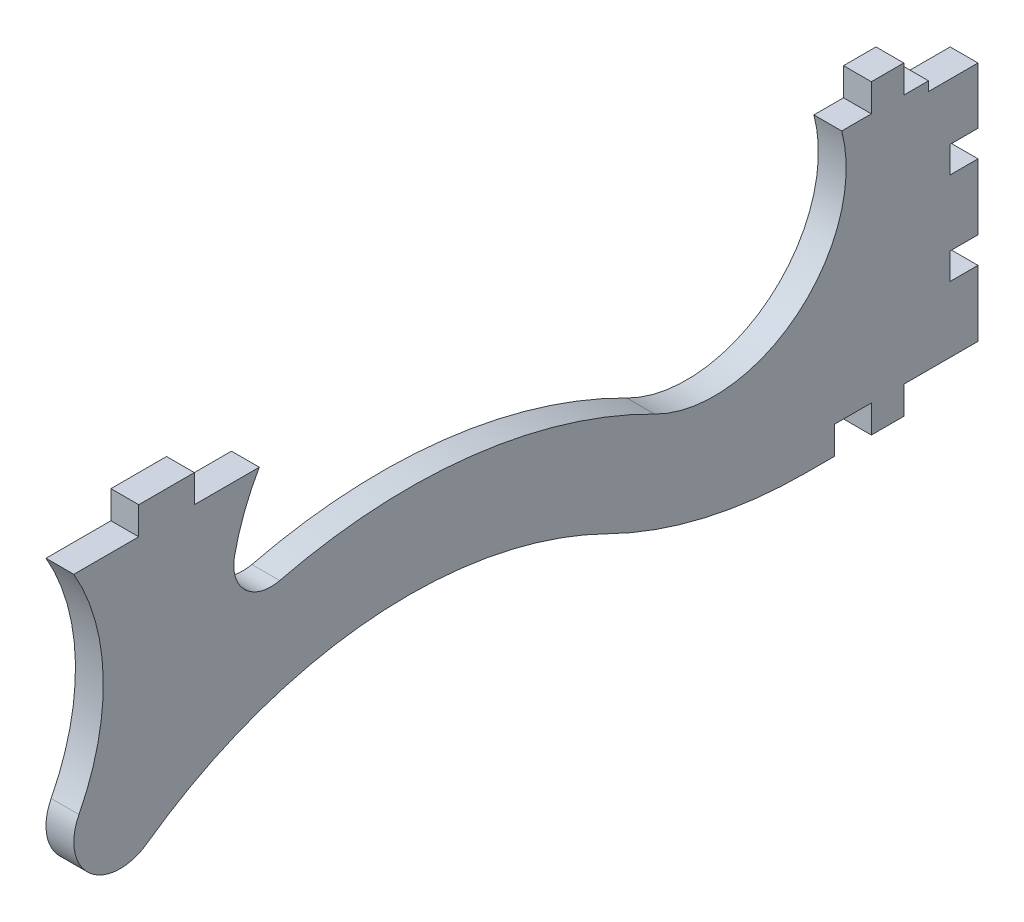
SolidWorks part; units mm, degrees
ref_plane "Front Plane" through (0, 0, 0) normal (0, 0, 1) x (1, 0, 0)
ref_plane "Top Plane" through (0, 0, 0) normal (0, 1, 0) x (1, 0, 0)
ref_plane "Right Plane" through (0, 0, 0) normal (1, 0, 0) x (0, 0, -1)
sketch "Sketch1" plane through (0, 0, 0) normal (1, 0, 0) x (0, 0, -1)
  line L0 (-80, 30) -> (-87, 30)
  line L1 (-87, 30) -> (-87, 33)
  line L2 (-87, 33) -> (-93, 33)
  line L3 (-93, 33) -> (-93, 30)
  line L4 (-93, 30) -> (-100, 30)
  line L19 (55, 0) -> (-55, 0) construction
  line L20 (0, -1000) -> (0, 49000) construction
  line L21 (-1.5, 18.6204) -> (-1.5, 0) construction
  line L22 (55, 30) -> (-55, 30) construction
  line L23 (-95, 0) -> (0, 0) construction
  line L24 (-100, 30) -> (-100, 5) construction
  line L25 (-18, 0) -> (-21, 0)
  line L26 (-100, 30) -> (-82.6795, 0) construction
  line L27 (-18, 0) -> (-18, 3)
  line L28 (-18, 3) -> (-14, 3)
  line L29 (-14, 3) -> (-14, 0)
  line L30 (-14, 0) -> (-10.5, 0)
  line L31 (-10.5, 0) -> (-10.5, 3)
  line L32 (-10.5, 3) -> (-2.5, 3)
  line L33 (-2.5, 3) -> (-2.5, 10.1)
  line L34 (-2.5, 10.1) -> (-5.5, 10.1)
  line L35 (-5.5, 10.1) -> (-5.5, 12.95)
  line L36 (-5.5, 12.95) -> (-2.5, 12.95)
  line L37 (-2.5, 12.95) -> (-2.5, 20.05)
  line L38 (-2.5, 20.05) -> (-5.5, 20.05)
  line L39 (-5.5, 20.05) -> (-5.5, 22.9)
  line L40 (-5.5, 22.9) -> (-2.5, 22.9)
  line L41 (-2.5, 22.9) -> (-2.5, 30)
  line L42 (-2.5, 30) -> (-10.5, 30)
  line L43 (-10.5, 30) -> (-10.5, 33)
  line L44 (-10.5, 33) -> (-14, 33)
  line L45 (-14, 33) -> (-14, 30)
  line L46 (-14, 30) -> (-17.1962, 30)
  line L47 (-80, 30) -> (-97.3205, 0) construction
  line L48 (-17.1962, 30) -> (-9.1577, 0) construction
  line L49 (-37.3737, 13.6485) -> (-42.4358, 5) construction
  line L50 (-63.8715, 20) -> (-63.8715, 10) construction
  line L51 (-63.8715, 10) -> (-63.8715, 0) construction
  arc A0 (-100, 30) -> (-99.4467, 7.2862) centre (-120.5494, 18.1358) cw
  arc A1 (-99.4467, 7.2862) -> (-92.088, 0.9355) centre (-95, 5) ccw
  arc A2 (-92.088, 0.9355) -> (-42.4358, 5) centre (-63.8715, -38.4492) cw
  arc A3 (-42.4358, 5) -> (-21, 0) centre (-21, 48.4492) ccw
  arc A4 (-80, 30) -> (-82.67, 23.0244) centre (-59.4506, 18.1358) ccw
  arc A7 (-82.67, 23.0244) -> (-77.8024, 18.3156) centre (-78.7558, 22.2003) ccw
  arc A8 (-77.8024, 18.3156) -> (-37.3737, 13.6485) centre (-63.8715, -38.4492) cw
  arc A9 (-17.1962, 30) -> (-37.3737, 13.6485) centre (-30.9285, 26.3204) cw
  point P18 (-5.5, 11.525)
  point P35 (-90, 33)
  point P52 (-5.5, 21.475)
  point P53 (-2.5, 16.5)
  point P58 (-18, 33)
  dimension "D7" = 5
  dimension "D16" = 4
  dimension "D18" = 10
  dimension "D1" = 4
  dimension "D2" = 1.5
  dimension "D3" = 3
  dimension "D4" = 2.85
  dimension "D5" = 6
  dimension "D6" = 3
  dimension "D8" = 3
  dimension "D9" = 30
  dimension "D10" = 3.5
  dimension "D11" = 1
  dimension "D12" = 3
  dimension "D15" = 60
  dimension "D17" = 15
  dimension "D19" = 5
extrude "Boss-Extrude1" add sketch "Sketch1" along normal blind 1.5 and the other way blind 1.5
sketch "Sketch2" plane through (1.5, 0, 0) normal (1, 0, 0) x (0, 0, -1)
  line L0 (-10.5, 30) -> (-7.8333, 30) construction
  line L1 (-7.8333, 30) -> (-5.1667, 30)
  line L2 (-5.1667, 30) -> (-2.5, 30)
  line L3 (-7.8333, 30) -> (-7.8333, 29)
  line L4 (-7.8333, 29) -> (-2.5, 29)
  line L5 (-2.5, 29) -> (-2.5, 30)
  dimension "D1" = 1
extrude "Cut-Extrude1" cut sketch "Sketch2" against normal through all
